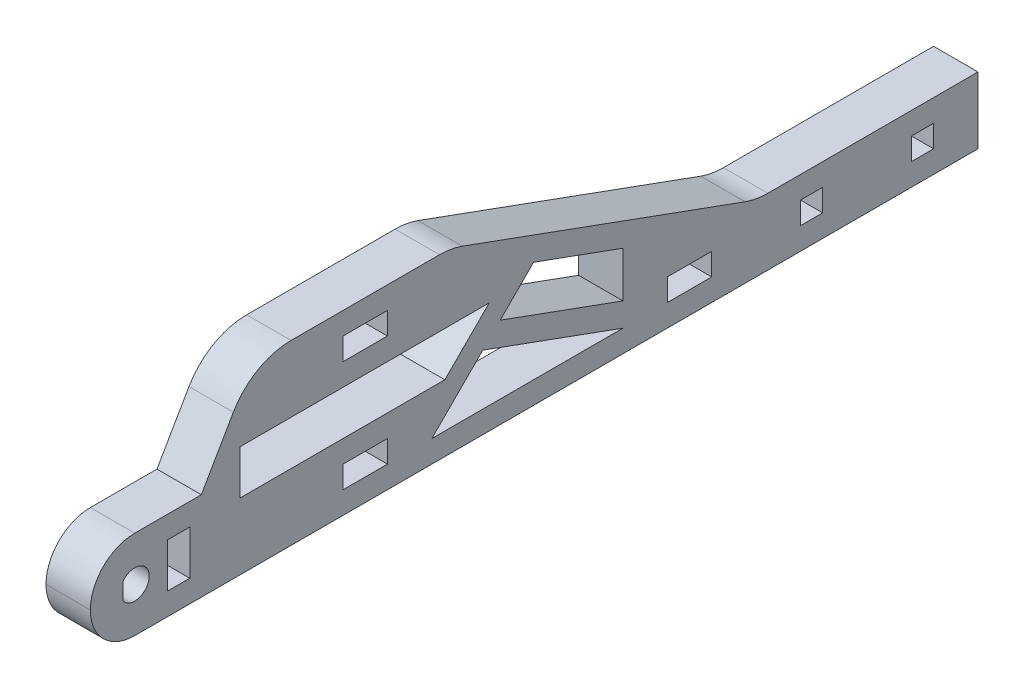
SolidWorks part; units mm, degrees
ref_plane "Front Plane" through (0, 0, 0) normal (0, 0, 1) x (1, 0, 0)
ref_plane "Top Plane" through (0, 0, 0) normal (0, 1, 0) x (1, 0, 0)
ref_plane "Right Plane" through (0, 0, 0) normal (1, 0, 0) x (0, 0, -1)
ref_plane "Plane1" through (0, 0, 0) normal (1, 0, 0) x (0, 0, -1)
sketch "Sketch1" plane through (0, 0, 0) normal (1, 0, 0) x (0, 0, -1)
  line L0 (0, 0) -> (200, 0)
  line L1 (200, 0) -> (200, 15)
  line L2 (200, 15) -> (150, 15)
  line L3 (150, 15) -> (81.3131, 40)
  line L7 (25, 20) -> (36.547, 40)
  line L8 (36.547, 40) -> (81.3131, 40)
  line L9 (0, 0) -> (0, 20)
  line L10 (0, 20) -> (25, 20)
  dimension "D1" = 200
  dimension "D2" = 15
  dimension "D3" = 50
  dimension "D4" = 160
  dimension "D5" = 25
  dimension "D6" = 20
  dimension "D7" = 20
  dimension "D8" = 120
extrude "Boss-Extrude1" add sketch "Sketch1" against normal blind 10
sketch "Sketch2" plane through (0, 0, 0) normal (1, 0, 0) x (0, 0, -1)
  line L20 (7.405, 11.9649) -> (7.405, 8.0351)
  line L23 (13.255, 19.5521) -> (13.255, 10.3168) construction
  line L26 (0, 20) -> (0, 0) construction
  arc A0 (7.405, 8.0351) -> (7.405, 11.9649) centre (10, 10) ccw
  point P0 (0, 10)
  dimension "D12" = 6.51
  dimension "D24" = 5.85
  dimension "D25" = 10
extrude "Cut-Extrude2" cut sketch "Sketch2" against normal through all
fillet "Fillet1" radius 10 2 edges at (-5, 0, 0) (-5, 20, 0)
fillet "Fillet2" radius 15 3 edges at (-5, 15, -150) (-5, 40, -81.3131) (-5, 40, -36.547)
sketch "Sketch3" plane through (0, 0, 0) normal (1, 0, 0) x (0, 0, -1)
  line L0 (7.405, 11.9649) -> (7.405, 8.0351) construction
  line L1 (17.405, 15) -> (22.405, 15)
  line L2 (17.405, 15) -> (17.405, 5)
  line L3 (17.405, 5) -> (22.405, 5)
  line L4 (22.405, 15) -> (22.405, 5)
  line L5 (17.405, 15) -> (22.405, 5) construction
  line L6 (17.405, 5) -> (22.405, 15) construction
  line L7 (56.9377, 35) -> (66.9377, 35)
  line L8 (56.9377, 35) -> (56.9377, 30)
  line L9 (56.9377, 30) -> (66.9377, 30)
  line L10 (66.9377, 35) -> (66.9377, 30)
  line L11 (56.9377, 35) -> (66.9377, 30) construction
  line L12 (56.9377, 30) -> (66.9377, 35) construction
  line L19 (56.9377, 10) -> (66.9377, 10)
  line L20 (56.9377, 10) -> (56.9377, 5)
  line L21 (56.9377, 5) -> (66.9377, 5)
  line L22 (66.9377, 10) -> (66.9377, 5)
  line L23 (56.9377, 10) -> (66.9377, 5) construction
  line L24 (56.9377, 5) -> (66.9377, 10) construction
  line L31 (130, 10) -> (140, 10)
  line L32 (130, 10) -> (130, 5)
  line L33 (130, 5) -> (140, 5)
  line L34 (140, 10) -> (140, 5)
  line L35 (130, 10) -> (140, 5) construction
  line L36 (130, 5) -> (140, 10) construction
  line L43 (78.6682, 40) -> (45.2073, 40) construction
  line L47 (200, 0) -> (200, 15) construction
  line L48 (10, 0) -> (200, 0) construction
  point P0 (19.905, 10)
  point P5 (61.9377, 32.5)
  point P11 (61.9377, 40)
  point P15 (61.9377, 7.5)
  point P25 (135, 7.5)
  dimension "D1" = 5
  dimension "D2" = 10
  dimension "D3" = 10
  dimension "D4" = 10
  dimension "D5" = 5
  dimension "D6" = 5
  dimension "D11" = 10
  dimension "D12" = 5
  dimension "D13" = 5
  dimension "D14" = 60
  dimension "D15" = 5
  dimension "D16" = 10
  dimension "D18" = 5
extrude "Cut-Extrude3" cut sketch "Sketch3" against normal through all both and the other way through all
sketch "Sketch4" plane through (0, 0, 0) normal (1, 0, 0) x (0, 0, -1)
  line L0 (33.6603, 25) -> (89.8666, 25)
  line L1 (89.8666, 25) -> (79.8666, 15)
  line L2 (79.8666, 15) -> (33.6603, 15)
  line L3 (33.6603, 15) -> (33.6603, 25)
  line L4 (88.4287, 16.491) -> (76.9377, 5)
  line L5 (76.9377, 5) -> (120, 5)
  line L6 (120, 5) -> (88.4287, 16.491)
  line L7 (66.9377, 30) -> (56.9377, 30) construction
  line L8 (56.9377, 10) -> (66.9377, 10) construction
  line L9 (10, 0) -> (200, 0) construction
  line L10 (32.2169, 32.5) -> (25, 20) construction
  line L11 (147.5146, 15.9046) -> (83.7985, 39.0954) construction
  line L12 (130, 5) -> (130, 10) construction
  line L16 (92.3297, 20.392) -> (99.8646, 27.9269)
  line L17 (99.8646, 27.9269) -> (120, 20.5982)
  line L18 (120, 20.5982) -> (120, 10.3209)
  line L19 (120, 10.3209) -> (92.3297, 20.392)
  line L20 (66.9377, 10) -> (66.9377, 5) construction
  dimension "D1" = 135
  dimension "D2" = 5
  dimension "D3" = 5
  dimension "D4" = 5
  dimension "D5" = 5
  dimension "D6" = 10
  dimension "D7" = 5
  dimension "D8" = 5
  dimension "D9" = 5
  dimension "D10" = 10
  dimension "D11" = 10
extrude "Cut-Extrude4" cut sketch "Sketch4" against normal through all both and the other way through all
sketch "Sketch5" plane through (0, 0, 0) normal (1, 0, 0) x (0, 0, -1)
  line L1 (185, 5) -> (190, 5)
  line L2 (185, 5) -> (185, 10)
  line L3 (185, 10) -> (190, 10)
  line L4 (190, 5) -> (190, 10)
  line L5 (185, 5) -> (190, 10) construction
  line L6 (185, 10) -> (190, 5) construction
  line L7 (160, 5) -> (165, 5)
  line L8 (160, 5) -> (160, 10)
  line L9 (160, 10) -> (165, 10)
  line L10 (165, 5) -> (165, 10)
  line L11 (160, 5) -> (165, 10) construction
  line L12 (160, 10) -> (165, 5) construction
  line L13 (200, 0) -> (200, 15) construction
  point P0 (187.5, 7.5)
  point P5 (162.5, 7.5)
  point P12 (200, 7.5)
  point P13 (190, 7.5)
  dimension "D1" = 5
  dimension "D2" = 5
  dimension "D3" = 10
  dimension "D4" = 20
  dimension "D5" = 5
  dimension "D6" = 5
extrude "Cut-Extrude5" cut sketch "Sketch5" against normal through all both and the other way through all
